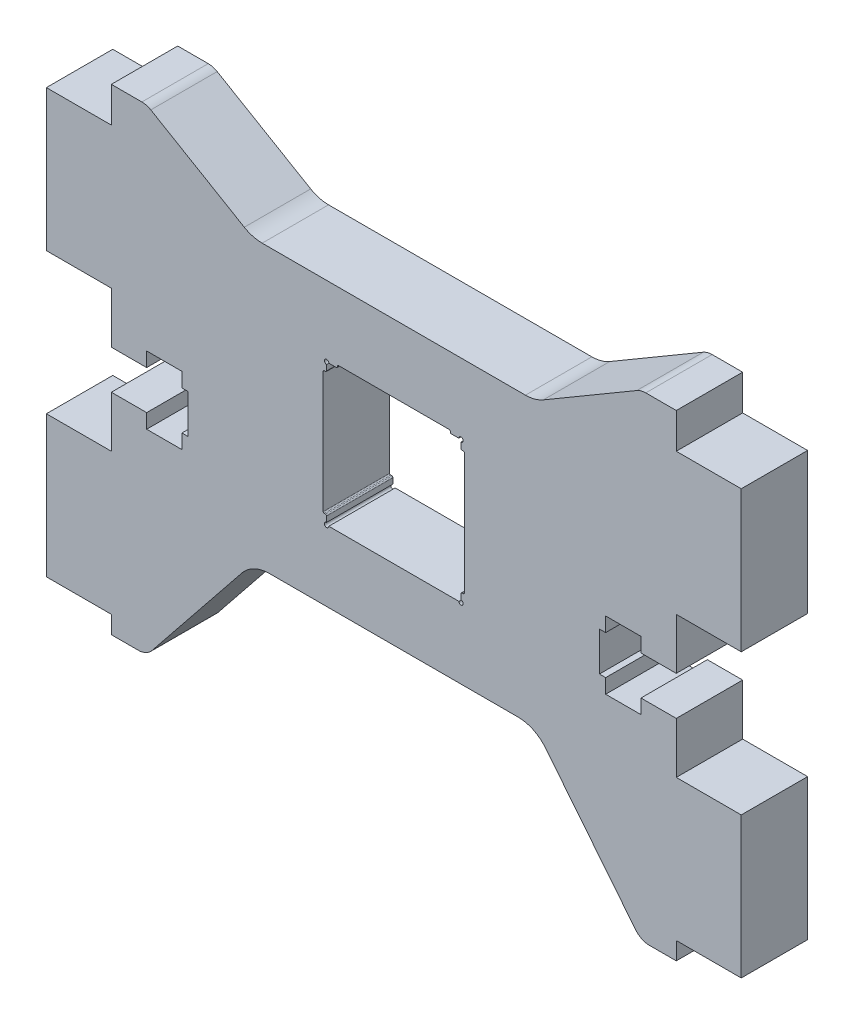
SolidWorks part; units mm, degrees
ref_plane "Front Plane" through (0, 0, 0) normal (0, 0, 1) x (1, 0, 0)
ref_plane "Top Plane" through (0, 0, 0) normal (0, 1, 0) x (1, 0, 0)
ref_plane "Right Plane" through (0, 0, 0) normal (1, 0, 0) x (0, 0, -1)
sketch "Sketch1" plane through (0, 0, 0) normal (0, 0, 1) x (1, 0, 0)
  line L0 (0, 0) -> (0, -22.987) construction
  line L1 (6.0452, -6.35) -> (-6.0452, -6.35)
  line L2 (6.0452, -6.35) -> (6.0452, 6.35)
  line L3 (6.0452, 6.35) -> (-6.0452, 6.35)
  line L4 (-6.0452, -6.35) -> (-6.0452, 6.35)
  line L5 (6.0452, -6.35) -> (-6.0452, 6.35) construction
  line L6 (6.0452, 6.35) -> (-6.0452, -6.35) construction
  line L7 (25.4, -22.987) -> (-25.4, -22.987) construction
  line L8 (25.4, 2.413) -> (25.4, -10.287)
  line L9 (25.4, -22.987) -> (31.242, -22.987)
  line L10 (-31.242, 2.413) -> (-25.4, 2.413)
  line L11 (31.242, -10.287) -> (25.4, -10.287)
  line L12 (31.242, -22.987) -> (31.242, -10.287)
  line L13 (25.4, -22.987) -> (25.4, -24.5745)
  line L14 (-12.7, -12.7) -> (12.7, -12.7)
  line L15 (12.7, -12.7) -> (22.225, -24.5745)
  line L16 (22.225, -24.5745) -> (25.4, -24.5745)
  line L17 (-12.7, 12.7) -> (12.7, 12.7)
  line L18 (-12.7, 12.7) -> (-22.225, 18.288)
  line L19 (-31.242, -10.287) -> (-25.4, -10.287)
  line L20 (-31.242, -22.987) -> (-31.242, -10.287)
  line L21 (-25.4, -22.987) -> (-31.242, -22.987)
  line L22 (-25.4, -22.987) -> (-25.4, -24.5745)
  line L23 (-22.225, -24.5745) -> (-25.4, -24.5745)
  line L24 (-12.7, -12.7) -> (-22.225, -24.5745)
  line L25 (-25.4, 18.288) -> (-22.225, 18.288)
  line L26 (-25.4, 2.413) -> (-25.4, -10.287)
  line L27 (31.242, 2.413) -> (25.4, 2.413)
  line L28 (31.242, 2.413) -> (31.242, 15.113)
  line L29 (31.242, 15.113) -> (25.4, 15.113)
  line L30 (25.4, 15.113) -> (25.4, 18.288)
  line L31 (25.4, 18.288) -> (22.225, 18.288)
  line L32 (-25.4, 15.113) -> (-25.4, 18.288)
  line L33 (12.7, 12.7) -> (22.225, 18.288)
  line L34 (-31.242, 15.113) -> (-25.4, 15.113)
  line L35 (-31.242, 2.413) -> (-31.242, 15.113)
  point P0 (0, 0)
  point P11 (0, -22.987)
  point P28 (0, -12.7)
  point P29 (0, 12.7)
  dimension "D1" = 12.7
  dimension "D2" = 12.0904
  dimension "D3" = 16.637
  dimension "D4" = 50.8
  dimension "D5" = 12.7
  dimension "D6" = 5.842
  dimension "D7" = 12.7
  dimension "D8" = 1.5875
  dimension "D9" = 12.7
  dimension "D10" = 6.35
  dimension "D11" = 3.175
  dimension "D12" = 6.35
  dimension "D13" = 12.7
  dimension "D16" = 12.7
  dimension "D17" = 3.175
  dimension "D18" = 3.175
extrude "Boss-Extrude1" add sketch "Sketch1" along normal blind 5.969
sketch "Sketch2" plane through (0, 0, 5.969) normal (0, 0, 1) x (1, 0, 0)
  line L0 (-25.4, -3.937) -> (25.4, -3.937) construction
  line L1 (-25.4, 2.413) -> (-25.4, -10.287) construction
  line L2 (25.4, -10.287) -> (25.4, 2.413) construction
  line L3 (22.225, -2.1844) -> (22.225, -0.889)
  line L4 (22.225, -5.6896) -> (25.4, -5.6896)
  line L5 (0, -3.937) -> (0, -12.7) construction
  line L6 (22.225, -2.1844) -> (25.4, -2.1844)
  line L7 (25.4, -5.6896) -> (25.4, -2.1844)
  line L8 (22.225, -5.6896) -> (25.4, -2.1844) construction
  line L9 (22.225, -2.1844) -> (25.4, -5.6896) construction
  line L10 (19.05, -6.985) -> (22.225, -6.985)
  line L11 (19.05, -6.985) -> (19.05, -5.6896)
  line L12 (19.05, -0.889) -> (22.225, -0.889)
  line L13 (22.225, -6.985) -> (22.225, -5.6896)
  line L14 (19.05, -6.985) -> (22.225, -0.889) construction
  line L15 (19.05, -0.889) -> (22.225, -6.985) construction
  line L16 (18.492, -5.6896) -> (19.05, -5.6896)
  line L17 (18.492, -5.6896) -> (18.492, -2.1844)
  line L18 (18.492, -2.1844) -> (19.05, -2.1844)
  line L19 (-12.7, -12.7) -> (12.7, -12.7) construction
  line L20 (18.492, -5.6896) -> (19.05, -2.1844) construction
  line L21 (18.492, -2.1844) -> (19.05, -5.6896) construction
  line L22 (19.05, -2.1844) -> (19.05, -0.889)
  line L23 (-18.492, -2.1844) -> (-19.05, -5.6896) construction
  line L24 (-18.492, -5.6896) -> (-19.05, -2.1844) construction
  line L25 (-19.05, -0.889) -> (-22.225, -6.985) construction
  line L26 (-19.05, -6.985) -> (-22.225, -0.889) construction
  line L27 (-22.225, -2.1844) -> (-25.4, -5.6896) construction
  line L28 (-22.225, -5.6896) -> (-25.4, -2.1844) construction
  line L29 (-19.05, -2.1844) -> (-19.05, -0.889)
  line L30 (-18.492, -2.1844) -> (-19.05, -2.1844)
  line L31 (-18.492, -5.6896) -> (-18.492, -2.1844)
  line L32 (-18.492, -5.6896) -> (-19.05, -5.6896)
  line L33 (-22.225, -6.985) -> (-22.225, -5.6896)
  line L34 (-19.05, -0.889) -> (-22.225, -0.889)
  line L35 (-19.05, -6.985) -> (-19.05, -5.6896)
  line L36 (-19.05, -6.985) -> (-22.225, -6.985)
  line L37 (-25.4, -5.6896) -> (-25.4, -2.1844)
  line L38 (-22.225, -2.1844) -> (-25.4, -2.1844)
  line L39 (-22.225, -5.6896) -> (-25.4, -5.6896)
  line L40 (-22.225, -2.1844) -> (-22.225, -0.889)
  point P6 (23.8125, -3.937)
  point P11 (20.6375, -3.937)
  point P16 (18.771, -3.937)
  point P37 (-18.771, -3.937)
  point P38 (-20.6375, -3.937)
  point P39 (-23.8125, -3.937)
  dimension "D1" = 3.175
  dimension "D2" = 3.175
  dimension "D3" = 3.5052
  dimension "D4" = 6.096
  dimension "D5" = 0.558
extrude "Cut-Extrude1" cut sketch "Sketch2" against normal through all
sketch "Sketch3" plane through (0, 0, 5.969) normal (0, 0, 1) x (1, 0, 0)
  line L0 (-6.0452, 0) -> (6.0452, 0) construction
  line L1 (-6.0452, 6.35) -> (-6.0452, -6.35) construction
  line L2 (6.0452, -6.35) -> (6.0452, 6.35) construction
  circle A0 centre (6.0452, 6.35) radius 0.1984
  circle A1 centre (-6.0452, 6.35) radius 0.1984
  circle A2 centre (-6.0452, -6.35) radius 0.1984
  circle A3 centre (6.0452, -6.35) radius 0.1984
  dimension "D1" = 0.3969
  dimension "D2" = 0.3969
extrude "Cut-Extrude2" cut sketch "Sketch3" against normal through all
fillet "Fillet1" radius 3.175 4 edges at (-12.7, -12.7, 2.9845) (12.7, -12.7, 2.9845) (12.7, 12.7, 2.9845) (-12.7, 12.7, 2.9845)
fillet "Fillet2" radius 1.5875 4 edges at (22.225, -24.5745, 2.9845) (-22.225, -24.5745, 2.9845) (-22.225, 18.288, 2.9845) (22.225, 18.288, 2.9845)
sketch "Sketch4" plane through (0, 0, 5.969) normal (0, 0, 1) x (1, 0, 0)
  line L0 (-6.0452, 0) -> (6.0452, 0) construction
  line L1 (-6.0452, 6.1516) -> (-6.0452, -6.1516) construction
  line L2 (6.0452, -6.1516) -> (6.0452, 6.1516) construction
  line L4 (6.35, -5.5562) -> (-6.35, -5.5563)
  line L5 (6.35, -5.5562) -> (6.35, 5.5563)
  line L6 (6.35, 5.5563) -> (-6.35, 5.5562)
  line L7 (-6.35, -5.5563) -> (-6.35, 5.5562)
  line L8 (6.35, -5.5562) -> (-6.35, 5.5562) construction
  line L9 (6.35, 5.5563) -> (-6.35, -5.5563) construction
  point P6 (0, 0)
  dimension "D1" = 12.7
  dimension "D2" = 11.1125
extrude "Cut-Extrude3" cut sketch "Sketch4" against normal through all
fillet "Fillet7" radius 0.1 8 edges at (6.35, -5.5562, 2.9845) (6.0452, -5.5562, 2.9845) (6.35, 5.5563, 2.9845) (6.0452, 5.5563, 2.9845) (-6.0452, 5.5562, 2.9845) (-6.35, 5.5562, 2.9845) (-6.35, -5.5563, 2.9845) (-6.0452, -5.5563, 2.9845)
sketch "Sketch5" plane through (0, 0, 5.969) normal (0, 0, 1) x (1, 0, 0)
  line L0 (5.8468, 6.35) -> (-5.8468, 6.35) construction
  line L1 (5.08, 6.1) -> (-5.08, 6.1)
  line L2 (5.08, 6.1) -> (5.08, 6.6)
  line L3 (5.08, 6.6) -> (-5.08, 6.6)
  line L4 (-5.08, 6.1) -> (-5.08, 6.6)
  line L5 (5.08, 6.1) -> (-5.08, 6.6) construction
  line L6 (5.08, 6.6) -> (-5.08, 6.1) construction
  point P0 (0, 6.35)
  dimension "D1" = 10.16
  dimension "D2" = 0.5
extrude "Cut-Extrude4" cut sketch "Sketch5" against normal through all
fillet "Fillet8" radius 0.1 4 edges at (5.08, 6.6, 2.9845) (5.08, 6.35, 2.9845) (-5.08, 6.6, 2.9845) (-5.08, 6.35, 2.9845)
